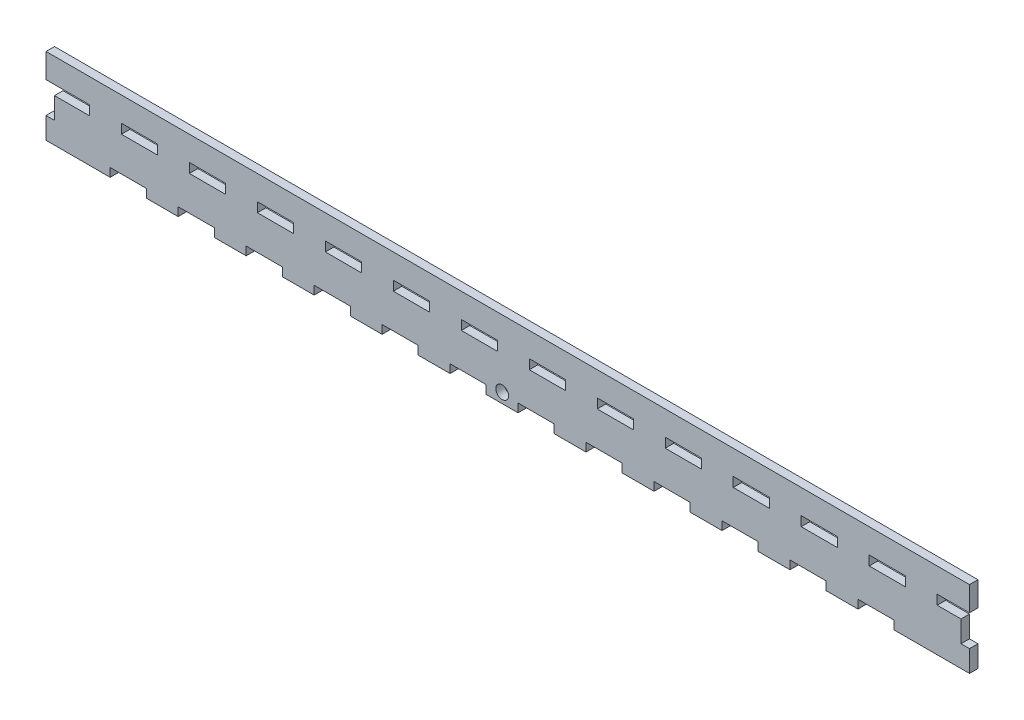
SolidWorks part; units mm, degrees
ref_plane "Plan de face" through (0, 0, 0) normal (0, 0, 1) x (1, 0, 0)
ref_plane "Plan de dessus" through (0, 0, 0) normal (0, 1, 0) x (1, 0, 0)
ref_plane "Plan de droite" through (0, 0, 0) normal (1, 0, 0) x (0, 0, -1)
sketch "Esquisse1" plane through (0, 0, 0) normal (0, 0, 1) x (1, 0, 0)
  line L6 (108.68, -6.055) -> (-108.68, -6.055)
  line L8 (108.68, -6.055) -> (108.68, 6.055)
  line L9 (108.68, 6.055) -> (-108.68, 6.055)
  line L10 (-108.68, -6.055) -> (-108.68, 6.055)
extrude "Boss.-Extru.1" add sketch "Esquisse1" along normal blind 2
sketch "Esquisse2" plane through (0, 0, 0) normal (0, 0, -1) x (-1, 0, 0)
  line L0 (-108.68, 6.055) -> (-101.32, 6.055) construction
  line L1 (-109.57, 4.055) -> (-101.07, 4.055)
  line L2 (-109.57, 4.055) -> (-109.57, 6.305)
  line L3 (-109.57, 6.305) -> (-101.07, 6.305)
  line L4 (-101.07, 4.055) -> (-101.07, 6.305)
  line L9 (-93.32, 4.055) -> (-93.32, 6.055) construction
  line L10 (-101.32, 6.055) -> (-101.32, 4.055) construction
  line L12 (-85.07, 4.055) -> (-85.07, 6.305)
  line L13 (-93.57, 6.305) -> (-85.07, 6.305)
  line L14 (-93.57, 4.055) -> (-93.57, 6.305)
  line L15 (-93.57, 4.055) -> (-85.07, 4.055)
  line L16 (-69.07, 4.055) -> (-69.07, 6.305)
  line L17 (-77.57, 6.305) -> (-69.07, 6.305)
  line L18 (-77.57, 4.055) -> (-77.57, 6.305)
  line L19 (-77.57, 4.055) -> (-69.07, 4.055)
  line L20 (-53.07, 4.055) -> (-53.07, 6.305)
  line L21 (-61.57, 6.305) -> (-53.07, 6.305)
  line L22 (-61.57, 4.055) -> (-61.57, 6.305)
  line L23 (-61.57, 4.055) -> (-53.07, 4.055)
  line L24 (-37.07, 4.055) -> (-37.07, 6.305)
  line L25 (-45.57, 6.305) -> (-37.07, 6.305)
  line L26 (-45.57, 4.055) -> (-45.57, 6.305)
  line L27 (-45.57, 4.055) -> (-37.07, 4.055)
  line L28 (-21.07, 4.055) -> (-21.07, 6.305)
  line L29 (-29.57, 6.305) -> (-21.07, 6.305)
  line L30 (-29.57, 4.055) -> (-29.57, 6.305)
  line L31 (-29.57, 4.055) -> (-21.07, 4.055)
  line L32 (-5.07, 4.055) -> (-5.07, 6.305)
  line L33 (-13.57, 6.305) -> (-5.07, 6.305)
  line L34 (-13.57, 4.055) -> (-13.57, 6.305)
  line L35 (-13.57, 4.055) -> (-5.07, 4.055)
  line L36 (10.93, 4.055) -> (10.93, 6.305)
  line L37 (2.43, 6.305) -> (10.93, 6.305)
  line L38 (2.43, 4.055) -> (2.43, 6.305)
  line L39 (2.43, 4.055) -> (10.93, 4.055)
  line L40 (26.93, 4.055) -> (26.93, 6.305)
  line L41 (18.43, 6.305) -> (26.93, 6.305)
  line L42 (18.43, 4.055) -> (18.43, 6.305)
  line L43 (18.43, 4.055) -> (26.93, 4.055)
  line L44 (42.93, 4.055) -> (42.93, 6.305)
  line L45 (34.43, 6.305) -> (42.93, 6.305)
  line L46 (34.43, 4.055) -> (34.43, 6.305)
  line L47 (34.43, 4.055) -> (42.93, 4.055)
  line L48 (58.93, 4.055) -> (58.93, 6.305)
  line L49 (50.43, 6.305) -> (58.93, 6.305)
  line L50 (50.43, 4.055) -> (50.43, 6.305)
  line L51 (50.43, 4.055) -> (58.93, 4.055)
  line L52 (74.93, 4.055) -> (74.93, 6.305)
  line L53 (66.43, 6.305) -> (74.93, 6.305)
  line L54 (66.43, 4.055) -> (66.43, 6.305)
  line L55 (66.43, 4.055) -> (74.93, 4.055)
  line L56 (90.93, 4.055) -> (90.93, 6.305)
  line L57 (82.43, 6.305) -> (90.93, 6.305)
  line L58 (82.43, 4.055) -> (82.43, 6.305)
  line L59 (82.43, 4.055) -> (90.93, 4.055)
  line L60 (90.68, 6.055) -> (90.68, 4.055) construction
  line L61 (98.68, 4.055) -> (98.68, 6.055) construction
  line L62 (98.43, 4.055) -> (108.93, 4.055)
  line L63 (98.43, 4.055) -> (98.43, 6.305)
  line L64 (98.43, 6.305) -> (108.93, 6.305)
  line L65 (108.93, 4.055) -> (108.93, 6.305)
  line L66 (108.68, 6.055) -> (108.68, -6.055) construction
  line L68 (108.68, 6.055) -> (98.68, 6.055) construction
  line L70 (-90.93, -4.055) -> (-82.43, -4.055)
  line L71 (-90.93, -4.055) -> (-90.93, -6.305)
  line L72 (-90.93, -6.305) -> (-82.43, -6.305)
  line L73 (-82.43, -4.055) -> (-82.43, -6.305)
  line L74 (-90.68, -6.055) -> (-90.68, -4.055) construction
  line L75 (-90.68, -6.055) -> (-82.68, -6.055) construction
  line L76 (-82.68, -6.055) -> (-82.68, -4.055) construction
  line L77 (-74.93, -4.055) -> (-74.93, -6.305)
  line L78 (-74.93, -4.055) -> (-66.43, -4.055)
  line L79 (-66.43, -4.055) -> (-66.43, -6.305)
  line L80 (-74.93, -6.305) -> (-66.43, -6.305)
  line L81 (-58.93, -4.055) -> (-58.93, -6.305)
  line L82 (-58.93, -4.055) -> (-50.43, -4.055)
  line L83 (-50.43, -4.055) -> (-50.43, -6.305)
  line L84 (-58.93, -6.305) -> (-50.43, -6.305)
  line L85 (-42.93, -4.055) -> (-42.93, -6.305)
  line L86 (-42.93, -4.055) -> (-34.43, -4.055)
  line L87 (-34.43, -4.055) -> (-34.43, -6.305)
  line L88 (-42.93, -6.305) -> (-34.43, -6.305)
  line L89 (-26.93, -4.055) -> (-26.93, -6.305)
  line L90 (-26.93, -4.055) -> (-18.43, -4.055)
  line L91 (-18.43, -4.055) -> (-18.43, -6.305)
  line L92 (-26.93, -6.305) -> (-18.43, -6.305)
  line L93 (-10.93, -4.055) -> (-10.93, -6.305)
  line L94 (-10.93, -4.055) -> (-2.43, -4.055)
  line L95 (-2.43, -4.055) -> (-2.43, -6.305)
  line L96 (-10.93, -6.305) -> (-2.43, -6.305)
  line L97 (5.07, -4.055) -> (5.07, -6.305)
  line L98 (5.07, -4.055) -> (13.57, -4.055)
  line L99 (13.57, -4.055) -> (13.57, -6.305)
  line L100 (5.07, -6.305) -> (13.57, -6.305)
  line L101 (21.07, -4.055) -> (21.07, -6.305)
  line L102 (21.07, -4.055) -> (29.57, -4.055)
  line L103 (29.57, -4.055) -> (29.57, -6.305)
  line L104 (21.07, -6.305) -> (29.57, -6.305)
  line L105 (37.07, -4.055) -> (37.07, -6.305)
  line L106 (37.07, -4.055) -> (45.57, -4.055)
  line L107 (45.57, -4.055) -> (45.57, -6.305)
  line L108 (37.07, -6.305) -> (45.57, -6.305)
  line L109 (53.07, -4.055) -> (53.07, -6.305)
  line L110 (53.07, -4.055) -> (61.57, -4.055)
  line L111 (61.57, -4.055) -> (61.57, -6.305)
  line L112 (53.07, -6.305) -> (61.57, -6.305)
  line L113 (69.07, -4.055) -> (69.07, -6.305)
  line L114 (69.07, -4.055) -> (77.57, -4.055)
  line L115 (77.57, -4.055) -> (77.57, -6.305)
  line L116 (69.07, -6.305) -> (77.57, -6.305)
  line L117 (85.07, -4.055) -> (85.07, -6.305)
  line L118 (85.07, -4.055) -> (93.57, -4.055)
  line L119 (93.57, -4.055) -> (93.57, -6.305)
  line L120 (85.07, -6.305) -> (93.57, -6.305)
  line L121 (93.32, -6.055) -> (93.32, -4.055) construction
  line L122 (-101.32, 4.055) -> (-108.68, 4.055) construction
  line L123 (-90.68, -4.055) -> (-82.68, -4.055) construction
  dimension "D1" = 0.25
  dimension "D2" = 0.25
  dimension "D3" = 0.25
  dimension "D6" = 0.25
  dimension "D7" = 0.25
  dimension "D8" = 0.25
  dimension "D10" = 0.25
  dimension "D12" = 0.25
  dimension "D13" = 0.25
  dimension "D14" = 0.25
  dimension "D16" = 0.25
  dimension "D5" = 13
  dimension "D15" = 12
extrude "Enlèv. mat.-Extru.1" cut sketch "Esquisse2" against normal through all
sketch "Esquisse4" plane through (0, 0, 0) normal (0, 0, -1) x (-1, 0, 0)
  line L0 (106.68, -1) -> (108.68, -1) construction
  line L1 (106.68, 4.055) -> (108.68, 4.055)
  line L2 (106.68, 4.055) -> (106.68, -1)
  line L3 (106.68, -1) -> (108.68, -1)
  line L4 (108.68, 4.055) -> (108.68, -1)
  line L5 (106.68, 4.055) -> (106.68, -1) construction
extrude "Enlèv. mat.-Extru.2" cut sketch "Esquisse4" against normal through all
mirror "Symétrie1" about plane through (0, 0, 0) normal (1, 0, 0) of "Enlèv. mat.-Extru.2"
sketch "Esquisse5" plane through (0, 0, 0) normal (0, 0, -1) x (-1, 0, 0)
  line L0 (108.68, -1) -> (108.68, -6.055) construction
  line L1 (-108.68, 12.055) -> (108.68, 12.055)
  line L2 (-108.68, 12.055) -> (-108.68, 6.055)
  line L3 (-108.68, 6.055) -> (108.68, 6.055)
  line L4 (108.68, 12.055) -> (108.68, 6.055)
  line L5 (108.68, 12.055) -> (106.68, 12.055) construction
  line L6 (90.93, 6.055) -> (98.43, 6.055) construction
  line L7 (-108.68, 6.305) -> (-108.68, 12.055) construction
extrude "Boss.-Extru.2" add sketch "Esquisse5" against normal up to surface (2 mm away) up to face at (0.0489, 0.1131, 2)
sketch "Esquisse6" plane through (0, 0, 0) normal (0, 0, -1) x (-1, 0, 0)
  line L0 (-85.07, 4.055) -> (-85.07, 6.055) construction
  line L1 (-93.57, 6.055) -> (-85.07, 6.055)
  line L2 (-93.57, 6.055) -> (-93.57, 6.305)
  line L3 (-93.57, 6.305) -> (-85.07, 6.305)
  line L4 (-85.07, 6.055) -> (-85.07, 6.305)
  line L5 (-77.57, 6.055) -> (-69.07, 6.055)
  line L6 (-77.57, 6.055) -> (-77.57, 6.305)
  line L7 (-77.57, 6.305) -> (-69.07, 6.305)
  line L8 (-69.07, 6.055) -> (-69.07, 6.305)
  line L9 (-61.57, 6.055) -> (-53.07, 6.055)
  line L10 (-61.57, 6.055) -> (-61.57, 6.305)
  line L11 (-61.57, 6.305) -> (-53.07, 6.305)
  line L12 (-53.07, 6.055) -> (-53.07, 6.305)
  line L13 (-45.57, 6.055) -> (-37.07, 6.055)
  line L14 (-45.57, 6.055) -> (-45.57, 6.305)
  line L15 (-45.57, 6.305) -> (-37.07, 6.305)
  line L16 (-37.07, 6.055) -> (-37.07, 6.305)
  line L17 (-29.57, 6.055) -> (-21.07, 6.055)
  line L18 (-29.57, 6.055) -> (-29.57, 6.305)
  line L19 (-29.57, 6.305) -> (-21.07, 6.305)
  line L20 (-21.07, 6.055) -> (-21.07, 6.305)
  line L21 (-13.57, 6.055) -> (-5.07, 6.055)
  line L22 (-13.57, 6.055) -> (-13.57, 6.305)
  line L23 (-13.57, 6.305) -> (-5.07, 6.305)
  line L24 (-5.07, 6.055) -> (-5.07, 6.305)
  line L25 (2.43, 6.055) -> (10.93, 6.055)
  line L26 (2.43, 6.055) -> (2.43, 6.305)
  line L27 (2.43, 6.305) -> (10.93, 6.305)
  line L28 (10.93, 6.055) -> (10.93, 6.305)
  line L29 (18.43, 6.055) -> (26.93, 6.055)
  line L30 (18.43, 6.055) -> (18.43, 6.305)
  line L31 (18.43, 6.305) -> (26.93, 6.305)
  line L32 (26.93, 6.055) -> (26.93, 6.305)
  line L33 (34.43, 6.055) -> (42.93, 6.055)
  line L34 (34.43, 6.055) -> (34.43, 6.305)
  line L35 (34.43, 6.305) -> (42.93, 6.305)
  line L36 (42.93, 6.055) -> (42.93, 6.305)
  line L37 (50.43, 6.055) -> (58.93, 6.055)
  line L38 (50.43, 6.055) -> (50.43, 6.305)
  line L39 (50.43, 6.305) -> (58.93, 6.305)
  line L40 (58.93, 6.055) -> (58.93, 6.305)
  line L41 (66.43, 6.055) -> (74.93, 6.055)
  line L42 (66.43, 6.055) -> (66.43, 6.305)
  line L43 (66.43, 6.305) -> (74.93, 6.305)
  line L44 (74.93, 6.055) -> (74.93, 6.305)
  line L45 (82.43, 6.055) -> (90.93, 6.055)
  line L46 (82.43, 6.055) -> (82.43, 6.305)
  line L47 (82.43, 6.305) -> (90.93, 6.305)
  line L48 (90.93, 6.055) -> (90.93, 6.305)
  line L53 (98.43, 6.055) -> (106.93, 6.055) [skipped]
  line L54 (98.43, 6.055) -> (98.43, 6.305) [skipped]
  line L55 (98.43, 6.305) -> (106.93, 6.305) [skipped]
  line L56 (106.93, 6.055) -> (106.93, 6.305) [skipped]
  line L57 (90.93, 4.055) -> (90.93, 6.055) construction
  line L58 (108.68, 6.055) -> (108.68, 12.055) construction
  line L59 (98.43, 6.055) -> (108.68, 6.055)
  line L60 (98.43, 6.055) -> (98.43, 6.305)
  line L61 (98.43, 6.305) -> (108.68, 6.305)
  line L62 (108.68, 6.055) -> (108.68, 6.305)
  line L63 (-108.68, 12.055) -> (-108.68, 6.055) construction
  line L64 (-101.07, 6.055) -> (-108.68, 6.055)
  line L65 (-101.07, 6.055) -> (-101.07, 6.305)
  line L66 (-101.07, 6.305) -> (-108.68, 6.305)
  line L67 (-108.68, 6.055) -> (-108.68, 6.305)
  dimension "D1" = 0.25
  dimension "D2" = 13
extrude "Enlèv. mat.-Extru.3" cut sketch "Esquisse6" against normal through all
sketch "Sketch1" plane through (0, 0, 0) normal (0, 0, -1) x (-1, 0, 0)
  circle A0 centre (1.32, -3.725) radius 1.5
  dimension "D1" = 3
extrude "Cut-Extrude1" cut sketch "Sketch1" against normal through all
